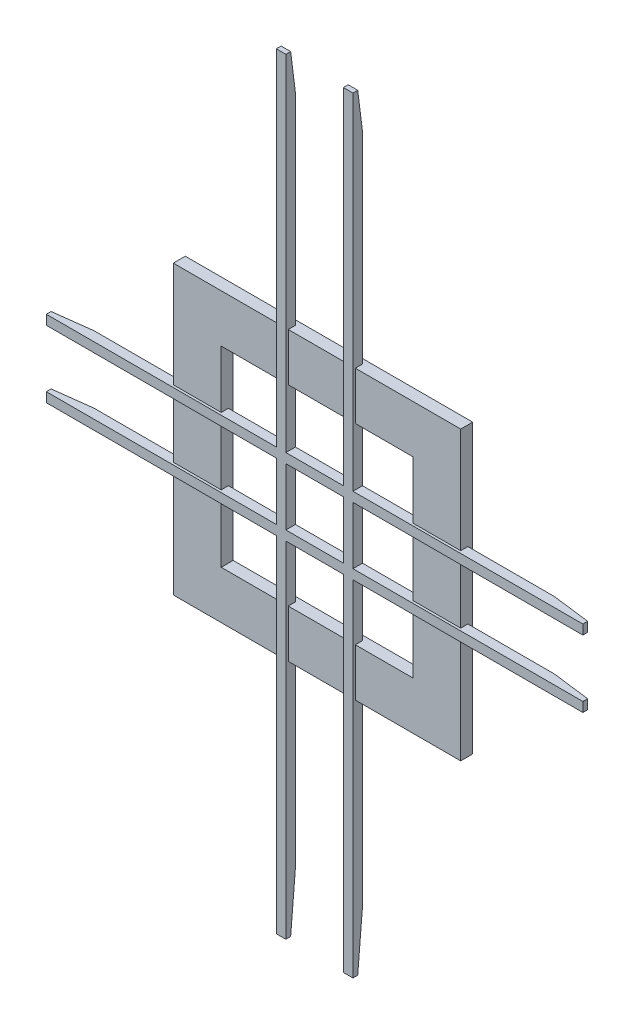
SolidWorks part; units mm, degrees
ref_plane "Front Plane" through (0, 0, 0) normal (0, 0, 1) x (1, 0, 0)
ref_plane "Top Plane" through (0, 0, 0) normal (0, 1, 0) x (1, 0, 0)
ref_plane "Right Plane" through (0, 0, 0) normal (1, 0, 0) x (0, 0, -1)
sketch "Sketch1" plane through (0, 0, 0) normal (0, 0, 1) x (1, 0, 0)
  line L0 (0, 0) -> (0, 50000) construction
  line L1 (177.8, 450.85) -> (-177.8, 450.85)
  line L2 (177.8, 450.85) -> (177.8, -450.85)
  line L3 (177.8, -450.85) -> (-177.8, -450.85)
  line L4 (-177.8, 450.85) -> (-177.8, -450.85)
  line L5 (177.8, 450.85) -> (-177.8, -450.85) construction
  line L6 (177.8, -450.85) -> (-177.8, 450.85) construction
  line L7 (-158.75, 431.8) -> (-158.75, -431.8)
  line L8 (158.75, -431.8) -> (-158.75, -431.8)
  line L9 (158.75, 431.8) -> (158.75, -431.8)
  line L10 (158.75, 431.8) -> (-158.75, 431.8)
  line L11 (-177.8, -57.15) -> (177.8, -57.15)
  line L12 (-95.25, 292.1) -> (95.25, 292.1)
  line L13 (-95.25, 292.1) -> (-95.25, 101.6)
  line L14 (-95.25, 101.6) -> (95.25, 101.6)
  line L15 (95.25, 292.1) -> (95.25, 101.6)
  line L16 (-95.25, 292.1) -> (95.25, 101.6) construction
  line L17 (-95.25, 101.6) -> (95.25, 292.1) construction
  line L18 (63.5, 260.35) -> (-63.5, 260.35)
  line L19 (63.5, 260.35) -> (63.5, 133.35)
  line L20 (63.5, 133.35) -> (-63.5, 133.35)
  line L21 (-63.5, 260.35) -> (-63.5, 133.35)
  line L22 (63.5, 260.35) -> (-63.5, 133.35) construction
  line L23 (63.5, 133.35) -> (-63.5, 260.35) construction
  line L24 (-177.8, 222.25) -> (177.8, 222.25)
  line L25 (-177.8, 222.25) -> (-177.8, 215.9)
  line L26 (-177.8, 215.9) -> (177.8, 215.9)
  line L27 (177.8, 222.25) -> (177.8, 215.9)
  line L28 (177.8, 171.45) -> (-177.8, 171.45)
  line L29 (177.8, 171.45) -> (177.8, 177.8)
  line L30 (177.8, 177.8) -> (-177.8, 177.8)
  line L31 (-177.8, 171.45) -> (-177.8, 177.8)
  line L32 (-19.05, 450.85) -> (-25.4, 450.85)
  line L33 (-19.05, 450.85) -> (-19.05, -57.15)
  line L35 (-25.4, 450.85) -> (-25.4, -57.15)
  line L36 (25.4, 450.85) -> (19.05, 450.85)
  line L37 (25.4, 450.85) -> (25.4, -57.15)
  line L39 (19.05, 450.85) -> (19.05, -57.15)
  point P0 (0, 0)
  point P12 (0, 196.85)
  point P17 (0, 196.85)
  dimension "D1" = 355.6
  dimension "D2" = 901.7
  dimension "D4" = 31.75
  dimension "D5" = 190.5
  dimension "D6" = 254
  dimension "D7" = 6.35
  dimension "D8" = 6.35
  dimension "D9" = 38.1
  dimension "D10" = 38.1
  dimension "D11" = 6.35
  dimension "D12" = 6.35
  dimension "D13" = 38.1
  dimension "D14" = 38.1
  dimension "D15" = 254
  dimension "D3" = 19.05
extrude "Boss-Extrude1" add sketch "Sketch1" along normal blind 4.7625 contours L35 L20 L21 L28 L13 L14 | L30 L21 L26 L13 | L21 L30 L13 L28 | L13 L26 L21 L24 | L35 L12 L13 L24 L21 L18 | L12 L35 L18 L33 | L39 L12 L33 L18 | L12 L39 L18 L37 | L12 L37 L18 L19 L24 L15 | L19 L26 L15 L24 | L30 L15 L26 L19 | L15 L30 L19 L28 | L20 L37 L14 L15 L28 L19 | L20 L39 L14 L37 | L39 L20 L33 L14 | L20 L35 L14 L33 region at (22.225, 276.225, 0) region at (67.0485, 263.8985, 0) region at (79.375, 219.075, 0) region at (0, 276.225, 0) region at (79.375, 196.85, 0) region at (-22.225, 276.225, 0) region at (79.375, 174.625, 0) region at (-67.0485, 263.8985, 0) region at (67.0485, 129.8015, 0) region at (-79.375, 219.075, 0) region at (22.225, 117.475, 0) region at (-79.375, 196.85, 0) region at (0, 117.475, 0) region at (-79.375, 174.625, 0) region at (-22.225, 117.475, 0) region at (-67.0485, 129.8015, 0)
extrude "Boss-Extrude2" add sketch "Sketch1<4>" against normal blind 3.175 contours L12 L37 L18 L19 L24 L15 | L12 L39 L18 L37 | L39 L12 L33 L18 | L12 L35 L18 L33 | L35 L12 L13 L24 L21 L18 | L13 L26 L21 L24 | L30 L21 L26 L13 | L21 L30 L13 L28 | L35 L20 L21 L28 L13 L14 | L20 L35 L14 L33 | L39 L20 L33 L14 | L20 L37 L14 L15 L28 L19 | L20 L39 L14 L37 | L15 L30 L19 L28 | L30 L15 L26 L19 | L19 L26 L15 L24 region at (22.225, 276.225, 0) region at (67.0485, 263.8985, 0) region at (79.375, 219.075, 0) region at (0, 276.225, 0) region at (79.375, 196.85, 0) region at (-22.225, 276.225, 0) region at (79.375, 174.625, 0) region at (-67.0485, 263.8985, 0) region at (67.0485, 129.8015, 0) region at (-79.375, 219.075, 0) region at (22.225, 117.475, 0) region at (-79.375, 196.85, 0) region at (0, 117.475, 0) region at (-79.375, 174.625, 0) region at (-22.225, 117.475, 0) region at (-67.0485, 129.8015, 0)
sketch "Sketch1<4>" plane through (0, 0, 0) normal (0, 0, 1) x (1, 0, 0) same geometry as "Sketch1"
extrude "Boss-Extrude3" add sketch "Sketch1<5>" along normal blind 6.35 contours L24 L37 L26 L19 | L15 L26 L9 L24 | L24 L39 L26 L37 | L39 L24 L33 L26 | L24 L35 L26 L33 | L35 L24 L21 L26 | L18 L35 L24 L33 | L18 L39 L24 L37 | L26 L39 L30 L37 | L26 L35 L30 L33 | L30 L35 L28 L33 | L39 L30 L33 L28 | L30 L39 L28 L37 | L30 L37 L28 L19 | L28 L39 L20 L37 | L28 L35 L20 L33 | L35 L30 L21 L28 | L7 L26 L13 L24 | L13 L30 L7 L28 | L7 L30 L4 L28 | L4 L26 L7 L24 | L10 L35 L12 L33 | L10 L39 L12 L37 | L1 L39 L10 L37 | L1 L35 L10 L33 | L9 L30 L15 L28 | L9 L26 L2 L24 | L2 L30 L9 L28 | L14 L39 L11 L37 | L14 L35 L11 L33 | L20 L35 L14 L33 | L20 L39 L14 L37 | L21 L30 L13 L28 | L13 L26 L21 L24 | L12 L35 L18 L33 | L12 L39 L18 L37 | L19 L26 L15 L24 | L15 L30 L19 L28 region at (22.225, 441.325, 0) region at (168.275, 219.075, 0) region at (22.225, 361.95, 0) region at (127, 219.075, 0) region at (-22.225, 441.325, 0) region at (22.225, 276.225, 0) region at (168.275, 174.625, 0) region at (79.375, 219.075, 0) region at (-22.225, 361.95, 0) region at (22.225, 241.3, 0) region at (127, 174.625, 0) region at (44.45, 219.075, 0) region at (-22.225, 276.225, 0) region at (22.225, 219.075, 0) region at (79.375, 174.625, 0) region at (-168.275, 219.075, 0) region at (-22.225, 241.3, 0) region at (0, 219.075, 0) region at (22.225, 196.85, 0) region at (44.45, 174.625, 0) region at (-127, 219.075, 0) region at (-22.225, 219.075, 0) region at (22.225, 174.625, 0) region at (22.225, 22.225, 0) region at (-168.275, 174.625, 0) region at (-79.375, 219.075, 0) region at (-44.45, 219.075, 0) region at (-22.225, 196.85, 0) region at (0, 174.625, 0) region at (22.225, 152.4, 0) region at (22.225, 117.475, 0) region at (-127, 174.625, 0) region at (-22.225, 174.625, 0) region at (-22.225, 22.225, 0) region at (-79.375, 174.625, 0) region at (-44.45, 174.625, 0) region at (-22.225, 152.4, 0) region at (-22.225, 117.475, 0)
sketch "Sketch1<5>" plane through (0, 0, 0) normal (0, 0, 1) x (1, 0, 0) same geometry as "Sketch1"
chamfer "Chamfer1" distance 25.4 distance2 3.175 3 edges at (-177.8, 174.625, 0) (-177.8, 219.075, 0) (22.225, 450.85, 0) first distance on face at (-136.525, 174.625, 0) first distance on face at (-136.525, 219.075, 0) first distance on face at (22.225, 371.475, 0)
chamfer "Chamfer2" distance 3.175 distance2 25.4 2 edges at (177.8, 174.625, 0) (177.8, 219.075, 0) first distance on face at (177.8, 174.625, 3.175) first distance on face at (177.8, 219.075, 3.175)
chamfer "Chamfer3" distance 38.1 distance2 3.175 2 edges at (-22.225, -57.15, 0) (22.225, -57.15, 0) first distance on face at (-22.225, 22.225, 0) first distance on face at (22.225, 22.225, 0)
